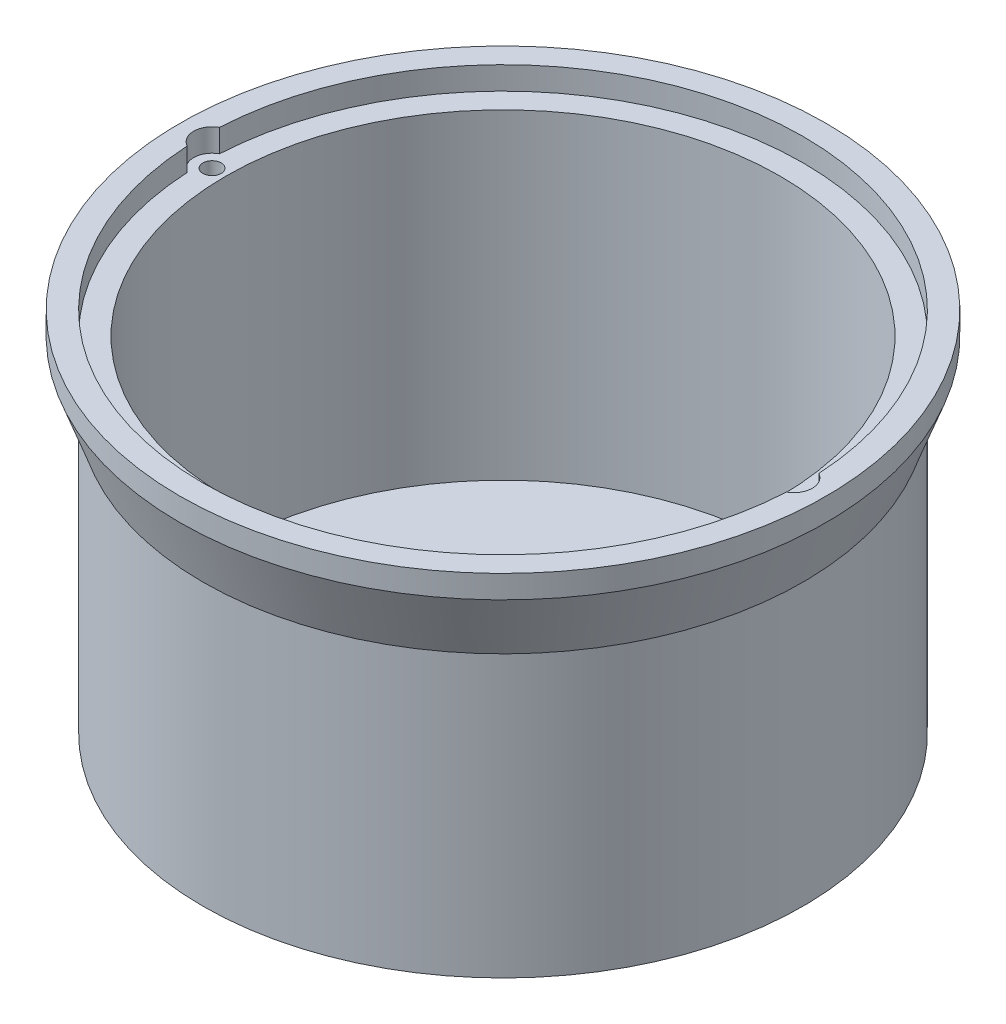
SolidWorks part; units mm, degrees
ref_plane "Front Plane" through (0, 0, 0) normal (0, 0, 1) x (1, 0, 0)
ref_plane "Top Plane" through (0, 0, 0) normal (0, 1, 0) x (1, 0, 0)
ref_plane "Right Plane" through (0, 0, 0) normal (1, 0, 0) x (0, 0, -1)
sketch "Sketch1" plane through (0, 0, 0) normal (0, 0, 1) x (1, 0, 0)
  line L0 (0, 93.6855) -> (0, -90.7684) construction
  line L1 (151.4677, 0) -> (-113.8812, 0) construction
  line L2 (0, 0) -> (-65.5, 0)
  line L3 (-65.5, 0) -> (-65.5, 61.2626)
  line L6 (-70.5, 80) -> (-65.5, 80)
  line L7 (-65.5, 80) -> (-65.5, 75)
  line L8 (-65.5, 75) -> (-60.5, 75)
  line L9 (-60.5, 75) -> (-60.5, 5)
  line L10 (-60.5, 5) -> (0, 5)
  line L11 (0, 5) -> (0, 0)
  line L13 (-70.5, 80) -> (-70.5, 75)
  line L14 (-70.5, 75) -> (-65.5, 61.2626)
  dimension "D1" = 5
  dimension "D2" = 5
  dimension "D3" = 10
  dimension "D4" = 5
  dimension "D5" = 20
  dimension "D6" = 80
  dimension "D7" = 5
  dimension "D8" = 65.5
revolve "Revolve1" add sketch "Sketch1" angle 360 about L11 region at (-32.75, 1.0663, 0)
sketch "Sketch2" plane through (0, 75, 0) normal (0, 1, 0) x (1, 0, 0)
  line L0 (0, 95.2886) -> (0, -107.3236) construction
  line L1 (126.4379, 0) -> (-144.7028, 0) construction
  circle A0 centre (-63.5, 0) radius 2
  circle A1 centre (-63.5, 0) radius 4
  circle A2 centre (63.5, 0) radius 4
  circle A3 centre (63.5, 0) radius 2
  dimension "D1" = 4
  dimension "D2" = 8
  dimension "D3" = 63.5
extrude "Cut-Extrude1" cut sketch "Sketch2" along normal through all
extrude "Cut-Extrude3" cut sketch "Sketch2<4>" against normal blind 3 contours A0 | A3 region at (-63.5, 75, 0) region at (63.5, 75, 0)
sketch "Sketch2<4>" plane through (0, 75, 0) normal (0, 1, 0) x (1, 0, 0) same geometry as "Sketch2"
